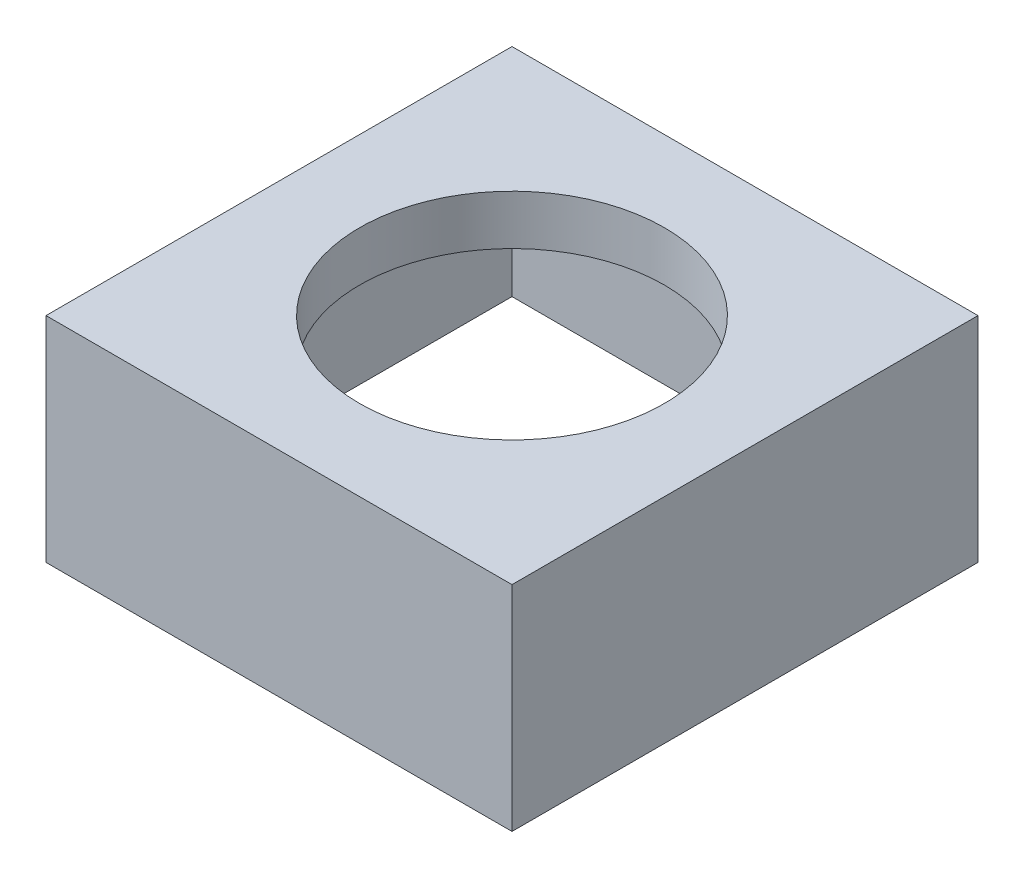
SolidWorks part; units mm, degrees
ref_plane "Front Plane" through (0, 0, 0) normal (0, 0, 1) x (1, 0, 0)
ref_plane "Top Plane" through (0, 0, 0) normal (0, 1, 0) x (1, 0, 0)
ref_plane "Right Plane" through (0, 0, 0) normal (1, 0, 0) x (0, 0, -1)
sketch "Sketch1" plane through (0, 0, 0) normal (0, 1, 0) x (1, 0, 0)
  line L1 (-248.5, -248.5) -> (248.5, -248.5)
  line L2 (-248.5, -248.5) -> (-248.5, 248.5)
  line L3 (-248.5, 248.5) -> (248.5, 248.5)
  line L4 (248.5, -248.5) -> (248.5, 248.5)
  line L5 (-248.5, -248.5) -> (248.5, 248.5) construction
  line L6 (-248.5, 248.5) -> (248.5, -248.5) construction
  line L7 (-245.5, -245.5) -> (245.5, -245.5)
  line L8 (-245.5, -245.5) -> (-245.5, 245.5)
  line L9 (-245.5, 245.5) -> (245.5, 245.5)
  line L10 (245.5, -245.5) -> (245.5, 245.5)
  line L11 (-245.5, -245.5) -> (245.5, 245.5) construction
  line L12 (-245.5, 245.5) -> (245.5, -245.5) construction
  point P0 (0, 0)
  point P5 (0, 0)
  dimension "D1" = 3
  dimension "D2" = 491
extrude "Boss-Extrude1" add sketch "Sketch1" along normal blind 225
sketch "Sketch2" plane through (0, 225, 0) normal (0, 1, 0) x (1, 0, 0)
  line L4 (248.5, -248.5) -> (248.5, 248.5)
  line L5 (248.5, 248.5) -> (-248.5, 248.5)
  line L6 (-248.5, 248.5) -> (-248.5, -248.5)
  line L7 (-248.5, -248.5) -> (248.5, -248.5)
  line L8 (248.5, -248.5) -> (248.5, 248.5)
  line L9 (248.5, 248.5) -> (-248.5, 248.5)
  line L10 (-248.5, 248.5) -> (-248.5, -248.5)
  line L11 (-248.5, -248.5) -> (248.5, -248.5)
  dimension "D1" = 0
extrude "Boss-Extrude2" add sketch "Sketch2" along normal blind 3
sketch "Sketch3" plane through (0, 228, 0) normal (0, 1, 0) x (1, 0, 0)
  circle A0 centre (0, 0) radius 162.5
  dimension "D1" = 325
extrude "Cut-Extrude1" cut sketch "Sketch3" against normal up to next
sketch "Sketch4" plane through (0, 225, 0) normal (0, -1, 0) x (1, 0, 0)
  line L4 (245.5, -245.5) -> (245.5, 245.5)
  line L5 (245.5, 245.5) -> (-245.5, 245.5)
  line L6 (-245.5, 245.5) -> (-245.5, -245.5)
  line L7 (-245.5, -245.5) -> (245.5, -245.5)
  line L8 (245.5, -245.5) -> (245.5, 245.5)
  line L9 (245.5, 245.5) -> (-245.5, 245.5)
  line L10 (-245.5, 245.5) -> (-245.5, -245.5)
  line L11 (-245.5, -245.5) -> (245.5, -245.5)
  circle A0 centre (0, 0) radius 166
  circle A1 centre (0, 0) radius 162.5 construction
  circle A2 centre (0, 0) radius 162.5
  dimension "D2" = 3.5
  dimension "D1" = 0
extrude "Boss-Extrude3" add sketch "Sketch4" along normal blind 50 contours A0 | A2
